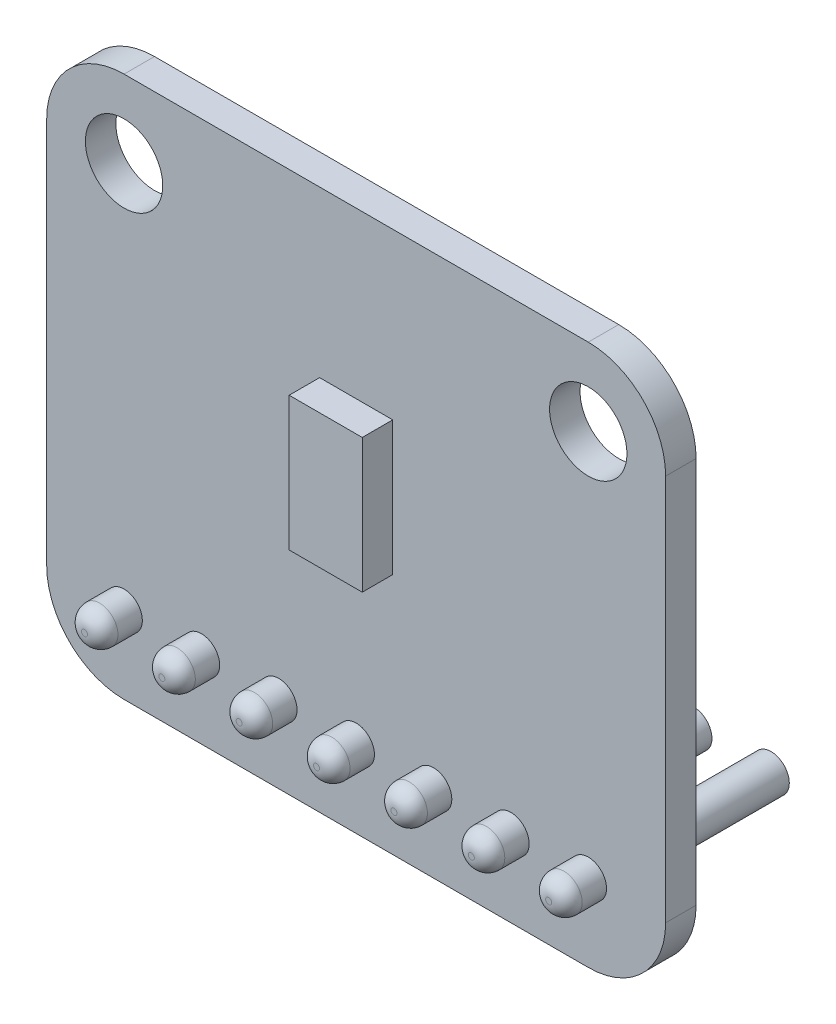
SolidWorks part; units mm, degrees
ref_plane "Front Plane" through (0, 0, 0) normal (0, 0, 1) x (1, 0, 0)
ref_plane "Top Plane" through (0, 0, 0) normal (0, 1, 0) x (1, 0, 0)
ref_plane "Right Plane" through (0, 0, 0) normal (1, 0, 0) x (0, 0, -1)
sketch "Sketch1" plane through (0, 0, 0) normal (0, 0, 1) x (1, 0, 0)
  line L1 (-10.16, 8.89) -> (10.16, 8.89)
  line L2 (-10.16, 8.89) -> (-10.16, -8.89)
  line L3 (-10.16, -8.89) -> (10.16, -8.89)
  line L4 (10.16, 8.89) -> (10.16, -8.89)
  line L5 (-10.16, 8.89) -> (10.16, -8.89) construction
  line L6 (-10.16, -8.89) -> (10.16, 8.89) construction
  point P0 (0, 0)
  dimension "D1" = 17.78
  dimension "D2" = 20.32
extrude "Boss-Extrude1" add sketch "Sketch1" along normal blind 1
fillet "Fillet2" radius 2.54 4 edges at (-10.16, -8.89, 0.5) (10.16, -8.89, 0.5) (10.16, 8.89, 0.5) (-10.16, 8.89, 0.5)
sketch "Sketch2" plane through (0, 0, 1) normal (0, 0, 1) x (1, 0, 0)
  line L0 (-10.16, 8.89) -> (-7.62, 6.35) construction
  line L2 (7.62, 8.89) -> (-7.62, 8.89) construction
  line L3 (-10.16, 6.35) -> (-10.16, -6.35) construction
  line L4 (0, 0) -> (0, 8.89) construction
  circle A0 centre (-7.62, 6.35) radius 1.27
  circle A1 centre (7.62, 6.35) radius 1.27
  dimension "D1" = 2.54
  dimension "D2" = 15.24
  dimension "D3" = 45
extrude "Cut-Extrude1" cut sketch "Sketch2" against normal through all
sketch "Sketch3" plane through (0, 0, 1) normal (0, 0, 1) x (1, 0, 0)
  line L0 (-7.62, -8.89) -> (7.62, -8.89) construction
  line L1 (-1.2, 3.47) -> (1.2, 3.47)
  line L2 (-1.2, 3.47) -> (-1.2, -0.93)
  line L3 (-1.2, -0.93) -> (1.2, -0.93)
  line L4 (1.2, 3.47) -> (1.2, -0.93)
  line L5 (-1.2, 3.47) -> (1.2, -0.93) construction
  line L6 (-1.2, -0.93) -> (1.2, 3.47) construction
  point P0 (0, 1.27)
  dimension "D1" = 10.16
  dimension "D2" = 4.4
  dimension "D3" = 2.4
extrude "Boss-Extrude2" add sketch "Sketch3" along normal blind 1
sketch "Sketch4" plane through (0, 0, 1) normal (0, 0, 1) x (1, 0, 0)
  line L0 (-10.16, -6.35) -> (10.16, -6.35) construction
  line L1 (-10.16, 6.35) -> (-10.16, -6.35) construction
  line L2 (10.16, -6.35) -> (10.16, 6.35) construction
  line L3 (-7.62, -6.35) -> (-10.16, -8.89) construction
  line L4 (-7.62, -8.89) -> (7.62, -8.89) construction
  line L5 (7.62, -6.35) -> (10.16, -8.89) construction
  circle A0 centre (-7.62, -6.35) radius 0.6
  circle A1 centre (-5.08, -6.35) radius 0.6
  circle A2 centre (-2.54, -6.35) radius 0.6
  circle A3 centre (0, -6.35) radius 0.6
  circle A4 centre (2.54, -6.35) radius 0.6
  circle A5 centre (5.08, -6.35) radius 0.6
  circle A6 centre (7.62, -6.35) radius 0.6
  dimension "D1" = 1.2
  dimension "D3" = 45
  dimension "D4" = 2.54
  dimension "D5" = 45
  dimension "D2" = 7
extrude "Boss-Extrude3" add sketch "Sketch4" along normal blind 1.3
extrude "Boss-Extrude4" add sketch "Sketch4<2>" against normal blind 6
sketch "Sketch4<2>" plane through (0, 0, 1) normal (0, 0, 1) x (1, 0, 0) same geometry as "Sketch4"
fillet "Fillet3" radius 0.5 7 edges at (3.14, -6.35, 2.3) (8.22, -6.35, 2.3) (5.68, -6.35, 2.3) (0.6, -6.35, 2.3) (-1.94, -6.35, 2.3) (-4.48, -6.35, 2.3) (-7.02, -6.35, 2.3)
